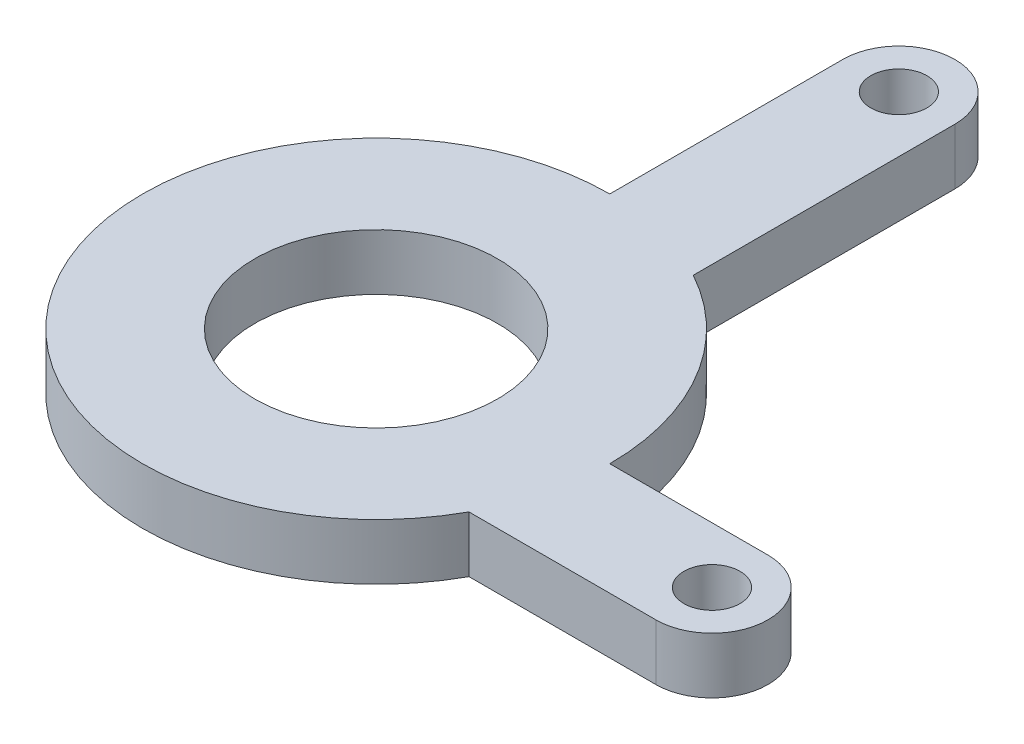
SolidWorks part; units mm, degrees
ref_plane "Front Plane" through (0, 0, 0) normal (0, 0, 1) x (1, 0, 0)
ref_plane "Top Plane" through (0, 0, 0) normal (0, 1, 0) x (1, 0, 0)
ref_plane "Right Plane" through (0, 0, 0) normal (1, 0, 0) x (0, 0, -1)
sketch "Sketch1" plane through (0, 0, 0) normal (0, 1, 0) x (1, 0, 0)
  line L0 (0, 12.5) -> (0, -12.5) construction
  line L1 (-12.5, 0) -> (12.5, 0) construction
  line L2 (0, 0) -> (-8.8388, 8.8388) construction
  line L3 (0, 0) -> (8.8388, 8.8388) construction
  line L6 (0, 12.5) -> (0, 24.9659)
  line L8 (6, 10.9659) -> (6, 24.9659)
  line L9 (12.5, 0) -> (20.9659, 0)
  line L11 (10.9659, -6) -> (20.9659, -6)
  arc A0 (0, 12.5) -> (10.9659, -6) centre (0, 0) ccw
  circle A1 centre (0, 0) radius 6.5
  arc A2 (6, 24.9659) -> (0, 24.9659) centre (3, 24.9659) ccw
  circle A3 centre (3, 24.9659) radius 1.5
  arc A4 (20.9659, -6) -> (20.9659, 0) centre (20.9659, -3) ccw
  arc A5 (12.5, 0) -> (6, 10.9659) centre (0, 0) ccw
  circle A6 centre (20.9659, -3) radius 1.5
  dimension "D1" = 25
  dimension "D2" = 13
  dimension "D5" = 6
  dimension "D6" = 3
  dimension "D9" = 6
  dimension "D10" = 3
  dimension "D3" = 6
  dimension "D4" = 14
  dimension "D7" = 6
  dimension "D8" = 10
extrude "Boss-Extrude1" add sketch "Sketch1" along normal blind 3 contours A1 | A0 L11 A4 L9 A5 L8 A2 L6 | A6 | A3 region at (0, 0, 0)
